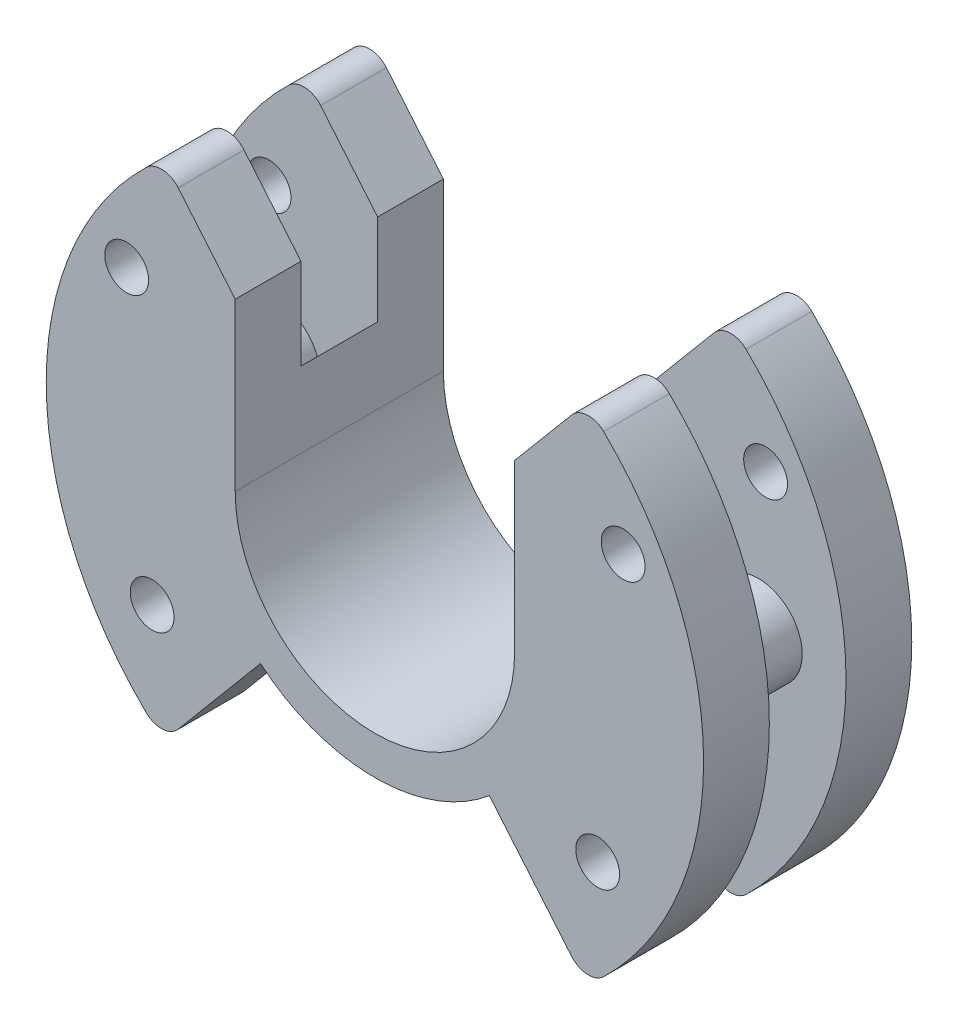
SolidWorks part; units mm, degrees
ref_plane "Front Plane" through (0, 0, 0) normal (0, 0, 1) x (1, 0, 0)
ref_plane "Top Plane" through (0, 0, 0) normal (0, 1, 0) x (1, 0, 0)
ref_plane "Right Plane" through (0, 0, 0) normal (1, 0, 0) x (0, 0, -1)
sketch "Sketch1" plane through (0, 0, 0) normal (0, 0, 1) x (1, 0, 0)
  circle A0 centre (0, 0) radius 30
  dimension "D1" = 60
extrude "Boss-Extrude1" add sketch "Sketch1" against normal blind 6
sketch "Sketch2" plane through (0, 0, 0) normal (0, 0, 1) x (1, 0, 0)
  circle A0 centre (0, 0) radius 14.5
  dimension "D1" = 29
extrude "Boss-Extrude2" add sketch "Sketch2" along normal blind 13
sketch "Sketch3" plane through (0, 0, 13) normal (0, 0, 1) x (1, 0, 0)
  circle A0 centre (0, 0) radius 12.75
  dimension "D1" = 25.5
extrude "Cut-Extrude1" cut sketch "Sketch3" against normal through all both and the other way through all
sketch "Sketch5" plane through (0, 0, 0) normal (0, 0, 1) x (1, 0, 0)
  circle A0 centre (0, 0) radius 30
  circle A1 centre (0, 0) radius 12.75
  circle A2 centre (0, 0) radius 12.75 construction
  circle A3 centre (0, 0) radius 30 construction
extrude "Boss-Extrude4" add sketch "Sketch5" against normal blind 6 from surface starting at face at (12.75, 0, 13)
sketch "Sketch6" plane through (0, 0, 0) normal (0, 0, 1) x (1, 0, 0)
  line L0 (-30, 0) -> (0, 0) construction
  line L1 (0, -41.069) -> (0, 41.069) construction
  line L2 (-40.6561, -12.75) -> (0, -12.75) construction
  line L3 (-20.3332, 0) -> (-20.3332, -41.5595) construction
  line L4 (-22.6592, 0) -> (-22.6592, 41.4208) construction
  line L6 (-40.6561, 12.75) -> (0, 12.75) construction
  circle A0 centre (0, 0) radius 12.75 construction
  circle A1 centre (-20.3332, -12.75) radius 2
  circle A2 centre (0, 0) radius 30 construction
  circle A4 centre (-22.6592, 12.75) radius 2
  circle A7 centre (20.3332, -12.75) radius 2
  circle A10 centre (22.6592, 12.75) radius 2
  dimension "D1" = 4
  dimension "D2" = 24
  dimension "D5" = 4
  dimension "D4" = 26
extrude "Cut-Extrude2" cut sketch "Sketch6" against normal through all both and the other way through all
sketch "Sketch7" plane through (0, 0, 13) normal (0, 0, 1) x (1, 0, 0)
  line L0 (0, 0) -> (-12.75, 0) construction
  line L1 (0, 0) -> (0, 12.75) construction
  line L2 (0, 0) -> (-27.5333, -32.8129) construction
  line L3 (0, 0) -> (27.5333, -32.8129) construction
  line L4 (10.4453, -12.4482) -> (19.2836, -22.9813)
  line L5 (-10.4453, 12.4482) -> (-19.2836, 22.9813)
  line L6 (-10.4453, -12.4482) -> (-19.2836, -22.9813)
  line L7 (10.4453, 12.4482) -> (19.2836, 22.9813)
  arc A0 (-10.4453, 12.4482) -> (10.4453, 12.4482) centre (0, 0) cw
  arc A1 (-19.2836, 22.9813) -> (19.2836, 22.9813) centre (0, 0) cw
  circle A4 centre (0, 0) radius 12.75 construction
  circle A5 centre (0, 0) radius 30 construction
  arc A6 (-10.4453, -12.4482) -> (10.4453, -12.4482) centre (0, 0) ccw
  arc A7 (-19.2836, -22.9813) -> (19.2836, -22.9813) centre (0, 0) ccw
  dimension "D2" = 3.5
  dimension "D1" = 50
  dimension "D3" = 50
extrude "Cut-Extrude3" cut sketch "Sketch7" against normal through all both and the other way through all
fillet "Fillet1" radius 2 1 edges at (-19.2836, -22.9813, 10) type face fillet first side face at (-14.8645, -17.7148, 10) second side face at (-24.6418, 0, 10)
fillet "Fillet2" radius 2 1 edges at (-19.2836, 22.9813, 10) type face fillet first side face at (-14.8645, 17.7148, 10) second side face at (-25.0303, 0.8951, 10)
fillet "Fillet3" radius 2 1 edges at (19.2836, 22.9813, 10) type face fillet first side face at (24.6418, 0, 10) second side face at (14.8645, 17.7148, 10)
fillet "Fillet4" radius 2 1 edges at (19.2836, -22.9813, 10) type face fillet first side face at (25.0303, -0.8951, 10) second side face at (14.8645, -17.7148, 10)
sketch "Sketch8" plane through (0, 0, 13) normal (0, 0, 1) x (1, 0, 0)
  line L0 (0, 42.8702) -> (0, -42.8702) construction
  line L1 (-42.07, 0) -> (42.07, 0) construction
  circle A9 centre (-22, 0) radius 4
  circle A11 centre (22, 0) radius 4
  dimension "D6" = 8
  dimension "D7" = 22
extrude "Boss-Extrude5" add sketch "Sketch8" against normal up to surface (13 mm away) up to face at (0, 0, 0)
fillet "Fillet5" radius 2 1 edges at (-19.2836, 22.9813, -3) type face fillet first side face at (-24.6418, 0, -3) second side face at (-14.8645, 17.7148, -3)
fillet "Fillet6" radius 2 1 edges at (-19.2836, -22.9813, -3) type face fillet first side face at (-25.0303, -0.8951, -3) second side face at (-14.8645, -17.7148, -3)
fillet "Fillet7" radius 2 1 edges at (19.2836, -22.9813, -3) type face fillet first side face at (14.8645, -17.7148, -3) second side face at (24.6418, 0, -3)
fillet "Fillet8" radius 2 1 edges at (19.2836, 22.9813, -3) type face fillet first side face at (14.8645, 17.7148, -3) second side face at (25.0303, 0.8951, -3)
sketch "Sketch10" plane through (0, 0, 13) normal (0, 0, 1) x (1, 0, 0)
  line L0 (0, 23.4531) -> (0, -27.6078) construction
  line L1 (-33.7286, -30) -> (35, -30) construction
  line L2 (-33.7286, -12.75) -> (35, -12.75) construction
  arc A1 (-20.8759, 21.5452) -> (-20.8759, -21.5452) centre (0, 0) ccw construction
sketch "Sketch11" plane through (0, 0, -6) normal (0, 0, -1) x (-1, 0, 0)
  line L4 (-12.75, 0) -> (-12.75, 25)
  line L5 (12.75, 0) -> (12.75, 25)
  line L6 (12.75, 25) -> (-12.75, 25)
  line L7 (-12.75, 0) -> (12.75, 0)
  circle A0 centre (0, 0) radius 12.75 construction
  dimension "D1" = 25
extrude "Cut-Extrude4" cut sketch "Sketch11" against normal through all both and the other way through all
